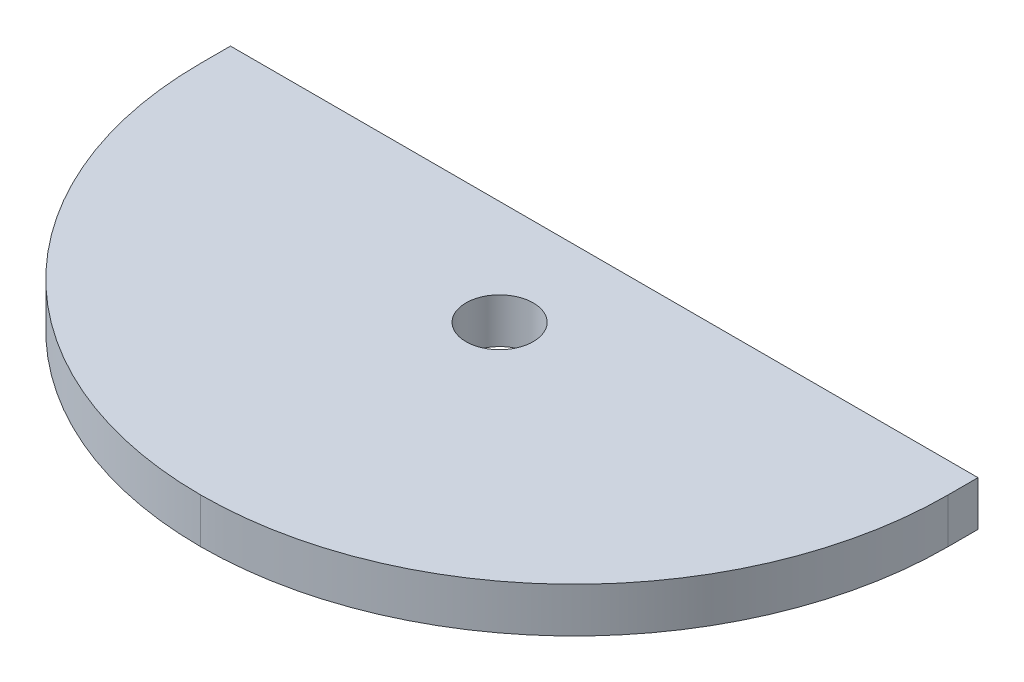
SolidWorks part; units mm, degrees
ref_plane "Front Plane" through (0, 0, 0) normal (0, 0, 1) x (1, 0, 0)
ref_plane "Top Plane" through (0, 0, 0) normal (0, 1, 0) x (1, 0, 0)
ref_plane "Right Plane" through (0, 0, 0) normal (1, 0, 0) x (0, 0, -1)
sketch "Sketch1" plane through (0, 0, 0) normal (0, 1, 0) x (1, 0, 0)
  line L1 (0, 0) -> (50, 0)
  line L2 (0, 0) -> (0, 27)
  line L3 (0, 27) -> (50, 27)
  line L4 (50, 0) -> (50, 27)
  dimension "D1" = 50
  dimension "D2" = 27
extrude "Boss-Extrude1" add sketch "Sketch1" along normal blind 3
fillet "Fillet1" radius 25 2 edges at (50, 1.5, 0) (0, 1.5, 0)
hole_wizard "M4 Clearance Hole2" positions "Sketch4" profile "Sketch5" hole size "M4" standard "ANSI Metric"
sketch "Sketch4" plane through (0, 3, 0) normal (0, 1, 0) x (1, 0, 0)
  line L0 (0, 27) -> (0, 25) construction
  point P0 (25, 20)
  dimension "D1" = 20
  dimension "D2" = 25
sketch "Sketch5" plane through (25, 3, -20) normal (1, 0, 0) x (0, 0, 1)
  line L0 (0, 0) -> (0, 4.3519)
  line L1 (0, 4.3519) -> (2.25, 3)
  line L2 (2.25, 3) -> (2.25, 0)
  line L5 (2.25, 0) -> (0, 0)
  line L10 (0, 4.3519) -> (-2.25, 3) construction
  line L11 (0, -6.35) -> (0, 107.95) construction
  dimension "Hole Dia." = 4.5
  dimension "Hole Depth" = 3
  dimension "Drill Angle" = 118
